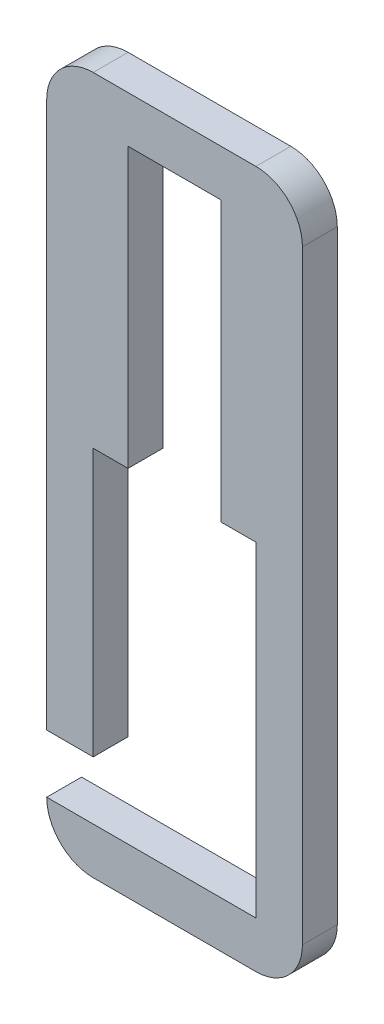
SolidWorks part; units mm, degrees
ref_plane "Спереди" through (0, 0, 0) normal (0, 0, 1) x (1, 0, 0)
ref_plane "Сверху" through (0, 0, 0) normal (0, 1, 0) x (1, 0, 0)
ref_plane "Справа" through (0, 0, 0) normal (1, 0, 0) x (0, 0, -1)
sketch "Эскиз1" plane through (0, 0, 0) normal (0, 0, 1) x (1, 0, 0)
  line L0 (4, 26) -> (-4, 26)
  line L1 (11, -30) -> (-11, -30)
  line L2 (11, -30) -> (11, 30)
  line L3 (11, 30) -> (-11, 30)
  line L4 (-11, -30) -> (-11, 30)
  line L5 (11, -30) -> (-11, 30) construction
  line L6 (11, 30) -> (-11, -30) construction
  line L7 (-7, -26) -> (-7, 2)
  line L8 (7, -26) -> (-7, -26)
  line L9 (7, -26) -> (7, 2)
  line L10 (-4, 2) -> (-7, 2)
  line L11 (-4, 2) -> (-4, 26)
  line L12 (0, -26) -> (0, 16) construction
  line L13 (4, 26) -> (4, 2)
  line L14 (4, 2) -> (7, 2)
  line L15 (7, 26) -> (-7, 26) construction
  line L17 (7, -26) -> (7, 26) construction
  line L18 (-7, -26) -> (-7, 26) construction
  point P0 (0, 0)
  dimension "D1" = 60
  dimension "D2" = 22
  dimension "D4" = 4
  dimension "D5" = 28
  dimension "D6" = 4
  dimension "D7" = 28
  dimension "D3" = 4
extrude "Бобышка-Вытянуть2" add sketch "Эскиз1" along normal blind 3
sketch "Эскиз2" plane through (0, 0, 3) normal (0, 0, 1) x (1, 0, 0)
  line L0 (-7, -26) -> (-11, -26)
  line L1 (-11, 30) -> (-11, -30) construction
  line L2 (-11, -26) -> (-11, -21)
  line L3 (-11, -21) -> (-7, -21)
  line L4 (-7, 2) -> (-7, -26) construction
  line L5 (-7, -21) -> (-7, -26)
  dimension "D1" = 5
extrude "Вырез-Вытянуть1" cut sketch "Эскиз2" against normal blind 5
fillet "Скругление1" radius 4 4 edges at (-11, -30, 1.5) (11, -30, 1.5) (11, 30, 1.5) (-11, 30, 1.5)
